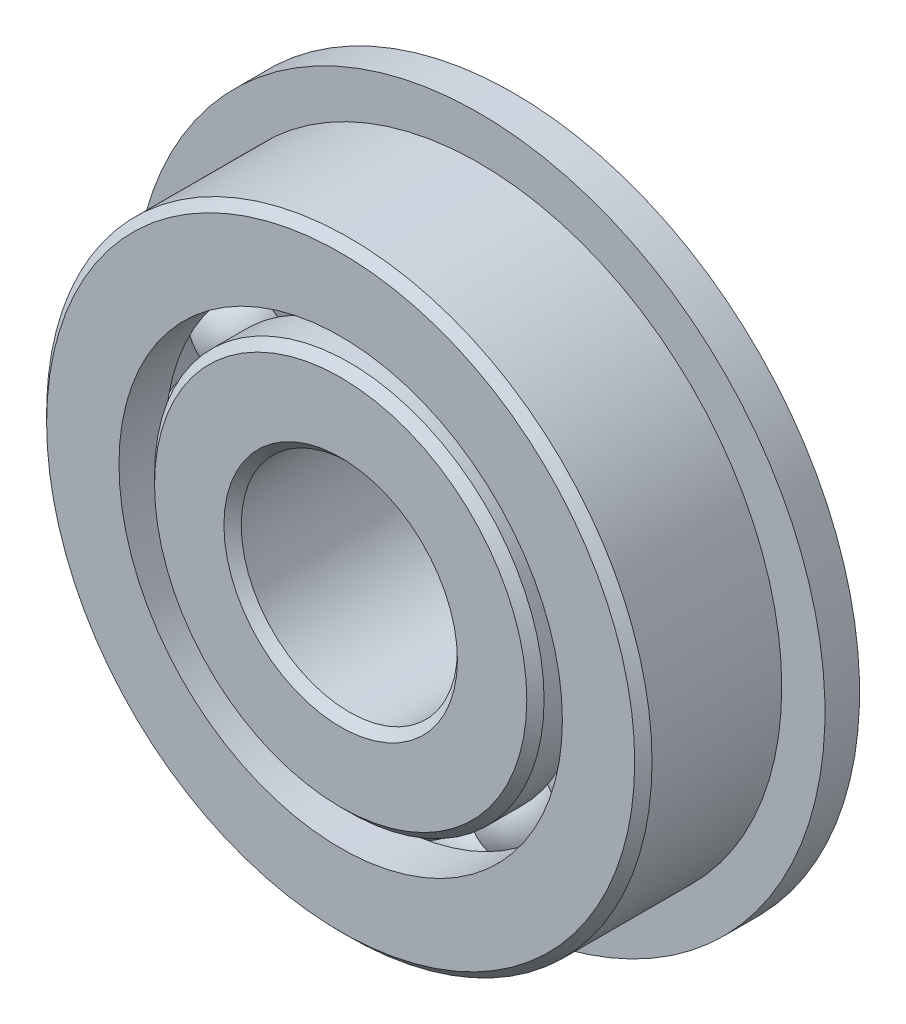
SolidWorks part; units mm, degrees
ref_plane "Front Plane" through (0, 0, 0) normal (0, 0, 1) x (1, 0, 0)
ref_plane "Top Plane" through (0, 0, 0) normal (0, 1, 0) x (1, 0, 0)
ref_plane "Right Plane" through (0, 0, 0) normal (1, 0, 0) x (0, 0, -1)
sketch "Sketch1" plane through (0, 0, 0) normal (1, 0, 0) x (0, 0, -1)
  line L0 (-3.175, 0) -> (3.175, 0) construction
  line L1 (0, 11.1125) -> (0, -11.1125) construction
  line L2 (2.8575, 11.1125) -> (-2.8575, 11.1125)
  line L3 (-2.8575, 11.1125) -> (-3.175, 10.795)
  line L4 (-3.175, 10.795) -> (-3.175, 8.1391)
  line L5 (-3.175, 8.1391) -> (-1.4704, 8.1391)
  line L6 (3.175, 8.1391) -> (1.4704, 8.1391)
  line L7 (3.175, 10.795) -> (3.175, 8.1391)
  line L8 (2.8575, 11.1125) -> (3.175, 10.795)
  line L9 (0, 11.1125) -> (0, 7.5406) construction
  line L10 (0, 7.5406) -> (0, 3.9688) construction
  line L11 (3.175, 7.1501) -> (3.175, -7.1501) construction
  line L12 (-3.175, 3.9688) -> (3.175, 3.9688) construction
  line L13 (0, 5.9531) -> (0, 3.9688) construction
  line L14 (0, 9.1281) -> (0, 11.1125) construction
  line L15 (3.175, 7.1501) -> (0, 7.1501) construction
  circle A1 centre (0, 7.5406) radius 1.5875 construction
  arc A2 (-1.4704, 8.1391) -> (1.4704, 8.1391) centre (0, 7.5406) cw
  point P14 (0, 3.9688)
  point P22 (0, 5.9531)
  point P23 (0, 9.1281)
  dimension "D3" = 3.175
  dimension "Width" = 6.35
  dimension "OD" = 22.225
  dimension "D1" = 45
  dimension "D2" = 0.3175
  dimension "D4" = 14.3002
  dimension "D5" = 1.978
  dimension "D6" = 0.989
revolve "Revolve1" add sketch "Sketch1" angle 360 about L0
sketch "Sketch3" plane through (0, 0, 0) normal (1, 0, 0) x (0, 0, -1)
  line L1 (-3.175, 10.795) -> (-3.175, 8.1391) construction
  line L2 (-2.8575, 11.1125) -> (-3.175, 10.795) construction
  line L3 (-3.175, 6.9421) -> (-3.175, 4.2862) construction
  line L4 (-3.175, 4.2862) -> (-3.175, 6.8326)
  line L5 (-3.175, 4.2862) -> (-2.8575, 3.9688)
  line L6 (-2.8575, 3.9688) -> (4.4577, 3.9688)
  line L7 (-3.175, 10.795) -> (-3.175, -10.795) construction
  line L8 (4.4577, 3.9688) -> (4.7752, 4.2862)
  line L9 (0, 0) -> (4.7752, 0) construction
  line L13 (2.8575, 11.1125) -> (3.175, 10.795) construction
  line L14 (-3.175, 6.8326) -> (-2.8575, 7.1501)
  line L15 (-2.8575, 7.1501) -> (-1.5387, 7.1501)
  line L16 (1.5387, 7.1501) -> (4.4577, 7.1501)
  line L17 (4.4577, 7.1501) -> (4.7752, 6.8326)
  line L18 (4.7752, 6.8326) -> (4.7752, 4.2862)
  circle A0 centre (0, 7.5406) radius 1.5875 construction
  arc A1 (-1.5387, 7.1501) -> (1.5387, 7.1501) centre (0, 7.5406) ccw
  dimension "D1" = 45
  dimension "Ring Wd" = 7.9502
  dimension "Inner Ring OD" = 14.3002
revolve "Revolve3" add sketch "Sketch3" angle 360 about L0
sketch "Sketch6" plane through (0, 0, 0) normal (1, 0, 0) x (0, 0, -1)
  line L1 (3.175, 8.1391) -> (1.905, 8.1391)
  line L2 (3.175, 8.1391) -> (3.175, 12.7)
  line L3 (3.175, 12.7) -> (1.905, 12.7)
  line L4 (1.905, 8.1391) -> (1.905, 12.7)
  line L5 (3.175, 0) -> (-3.175, 0) construction
  dimension "Flange OD" = 25.4
  dimension "Flange Thickness" = 1.27
revolve "Revolve6" add sketch "Sketch6" angle 360 about L5
sketch "Sketch4" plane through (0, 0, 0) normal (1, 0, 0) x (0, 0, -1)
  line L0 (-1.5875, 7.5406) -> (1.5875, 7.5406)
  circle A0 centre (0, 7.5406) radius 1.5875 construction
  arc A1 (1.5875, 7.5406) -> (-1.5875, 7.5406) centre (0, 7.5406) ccw
revolve "Revolve4" add sketch "Sketch4" angle 360 about L0
ref_axis "Axis1" through (0, 0, -3.175) along (0, 0, 1)
pattern_circular "CirPattern1" count 12 every 30 about axis through (0, 0, -3.175) along (0, 0, 1) of bodies 104
sketch "Sketch5" plane through (0, 0, 0) normal (1, 0, 0) x (0, 0, -1)
  line L0 (-3.175, 8.1391) -> (-1.4704, 8.1391) construction
  line L1 (-3.0162, 8.1391) -> (-1.5387, 8.1391)
  line L2 (-3.0162, 8.1391) -> (-3.0162, 7.1501)
  line L3 (-3.0162, 7.1501) -> (-1.5387, 7.1501)
  line L4 (-1.5387, 8.1391) -> (-1.5387, 7.1501)
  line L6 (3.175, 8.1391) -> (1.4704, 8.1391) construction
  line L7 (3.0162, 8.1391) -> (1.5387, 8.1391)
  line L8 (3.0162, 8.1391) -> (3.0162, 7.1501)
  line L9 (3.0162, 7.1501) -> (1.5387, 7.1501)
  line L10 (1.5387, 8.1391) -> (1.5387, 7.1501)
  line L12 (-2.8575, 11.1125) -> (-3.175, 10.795) construction
  line L13 (3.175, 7.1501) -> (0, 7.1501) construction
  line L15 (-2.8575, 7.1501) -> (-1.5387, 7.1501) construction
  line L16 (3.0162, 8.1391) -> (3.0162, 10.9538) construction
  line L17 (2.8575, 11.1125) -> (3.175, 10.795) construction
  point P18 (-3.0163, 10.9538)
revolve "Revolve5" [suppressed] add sketch "Sketch5" angle 360 about L0
equation "\"D2@Sketch1\" = \"Width@Sketch1\"*.05"
equation "\"D2@CirPattern1\" = 360/\"Balls@CirPattern1\""
equation "\"D4@Sketch1\"=\"Inner Ring OD@Sketch3\""
equation "\"D3@Sketch1\"=\"Width@Sketch1\"/2"
equation "\"D6@Sketch1\"=\"D5@Sketch1\"/2"
